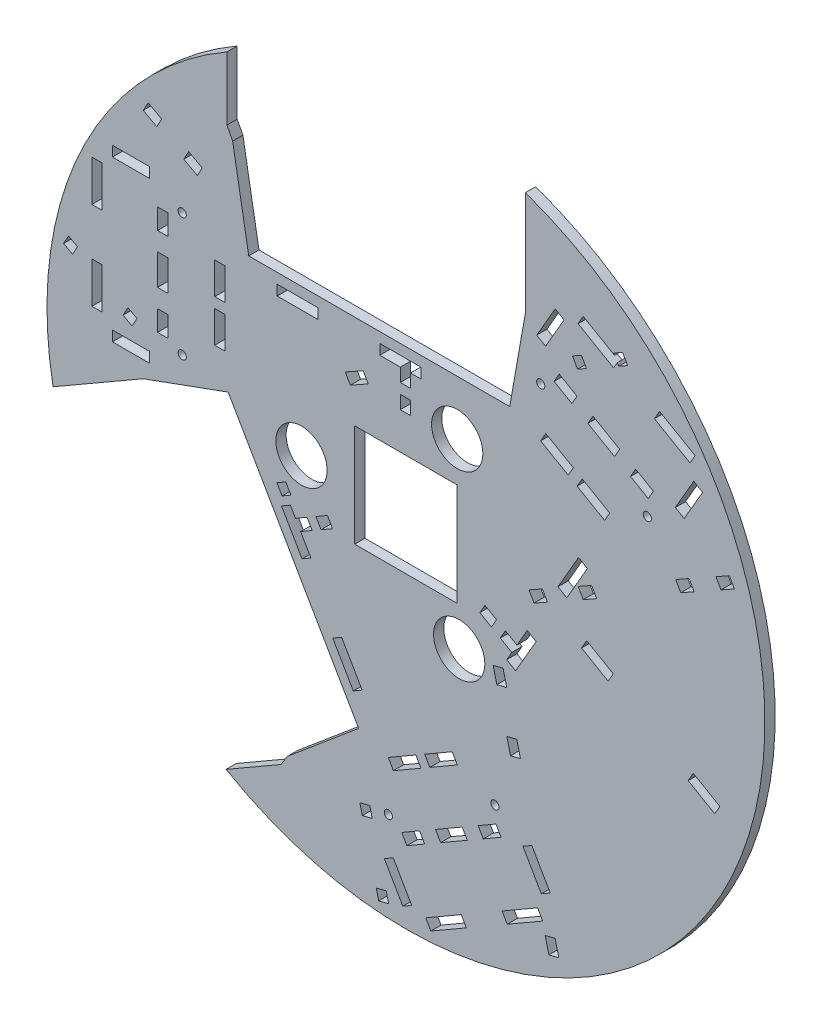
SolidWorks part; units mm, degrees
material "Balsa"
ref_plane "Plan de face" through (0, 0, 0) normal (0, 0, 1) x (1, 0, 0)
ref_plane "Plan de dessus" through (0, 0, 0) normal (0, 1, 0) x (1, 0, 0)
ref_plane "Plan de droite" through (0, 0, 0) normal (1, 0, 0) x (0, 0, -1)
sketch "Esquisse1" plane through (0, 0, 0) normal (0, 0, 1) x (1, 0, 0)
  circle A0 centre (148.0804, -12.1102) radius 175
  dimension "D1" = 350
extrude "Boss.-Extru.1" add sketch "Esquisse1" along normal blind 5
sketch "Esquisse2" plane through (0, 0, 5) normal (0, 0, 1) x (1, 0, 0)
  line L0 (135.3118, 53.7774) -> (135.3118, 48.7774)
  line L1 (5, 72.2774) -> (23, 72.2774)
  line L2 (5, 72.2774) -> (5, 67.2774)
  line L3 (5, 67.2774) -> (23, 67.2774)
  line L4 (23, 72.2774) -> (23, 67.2774)
  line L5 (-5, 62.2774) -> (0, 62.2774)
  line L6 (-5, 62.2774) -> (-5, 42.2774)
  line L7 (-5, 42.2774) -> (0, 42.2774)
  line L8 (0, 62.2774) -> (0, 42.2774)
  line L9 (-5, 19.2774) -> (0, 19.2774)
  line L10 (-5, 19.2774) -> (-5, -0.7226)
  line L11 (-5, -0.7226) -> (0, -0.7226)
  line L12 (0, 19.2774) -> (0, -0.7226)
  line L13 (5, -5.7226) -> (23, -5.7226)
  line L14 (5, -5.7226) -> (5, -10.7226)
  line L15 (5, -10.7226) -> (23, -10.7226)
  line L16 (23, -5.7226) -> (23, -10.7226)
  line L17 (27, 14.2774) -> (32, 14.2774)
  line L18 (27, 14.2774) -> (27, 4.2774)
  line L19 (27, 4.2774) -> (32, 4.2774)
  line L20 (32, 14.2774) -> (32, 4.2774)
  line L21 (27, 38.2774) -> (32, 38.2774)
  line L22 (27, 38.2774) -> (27, 23.2774)
  line L23 (27, 23.2774) -> (32, 23.2774)
  line L24 (32, 38.2774) -> (32, 23.2774)
  line L25 (27, 57.2774) -> (32, 57.2774)
  line L26 (27, 57.2774) -> (27, 47.2774)
  line L27 (27, 47.2774) -> (32, 47.2774)
  line L28 (32, 57.2774) -> (32, 47.2774)
  line L29 (54.86, 48.7774) -> (59.86, 48.7774)
  line L30 (54.86, 48.7774) -> (54.86, 33.2774)
  line L31 (54.86, 33.2774) -> (59.86, 33.2774)
  line L32 (59.86, 48.7774) -> (59.86, 33.2774)
  line L33 (54.86, 28.2774) -> (59.86, 28.2774)
  line L34 (54.86, 28.2774) -> (54.86, 12.7774)
  line L35 (54.86, 12.7774) -> (59.86, 12.7774)
  line L36 (59.86, 28.2774) -> (59.86, 12.7774)
  line L37 (85.3118, 53.7774) -> (105.3118, 53.7774)
  line L38 (85.3118, 53.7774) -> (85.3118, 48.7774)
  line L39 (85.3118, 48.7774) -> (105.3118, 48.7774)
  line L40 (105.3118, 53.7774) -> (105.3118, 48.7774)
  line L41 (145.3118, 37.2774) -> (150.3118, 37.2774)
  line L42 (145.3118, 37.2774) -> (145.3118, 30.7774)
  line L43 (145.3118, 30.7774) -> (150.3118, 30.7774)
  line L44 (150.3118, 37.2774) -> (150.3118, 30.7774)
  line L45 (135.3118, 48.7774) -> (145.3118, 48.7774)
  line L46 (155.3118, 48.7774) -> (135.3118, 48.7774) construction
  line L47 (145.3118, 48.7774) -> (145.3118, 42.2774)
  line L48 (145.3118, 42.2774) -> (150.3118, 42.2774)
  line L49 (150.3118, 42.2774) -> (150.3118, 48.7774)
  line L50 (150.3118, 48.7774) -> (155.3118, 48.7774)
  line L51 (155.3118, 48.7774) -> (155.3118, 53.7774)
  line L52 (155.3118, 53.7774) -> (135.3118, 53.7774)
  line L53 (292.7025, 69.6073) -> (283.7025, 54.0188)
  line L54 (292.7025, 69.6073) -> (288.3723, 72.1073)
  line L55 (288.3723, 72.1073) -> (279.3723, 56.5188)
  line L56 (283.7025, 54.0188) -> (279.3723, 56.5188)
  line L57 (289.0422, 83.2676) -> (286.5422, 78.9374)
  line L58 (289.0422, 83.2676) -> (271.7217, 93.2676)
  line L59 (271.7217, 93.2676) -> (269.2217, 88.9374)
  line L60 (286.5422, 78.9374) -> (269.2217, 88.9374)
  line L61 (251.8031, 104.7676) -> (249.3031, 100.4374)
  line L62 (251.8031, 104.7676) -> (234.4826, 114.7676)
  line L63 (234.4826, 114.7676) -> (231.9826, 110.4374)
  line L64 (249.3031, 100.4374) -> (231.9826, 110.4374)
  line L65 (225.1525, 108.6073) -> (216.1525, 93.0188)
  line L66 (225.1525, 108.6073) -> (220.8223, 111.1073)
  line L67 (220.8223, 111.1073) -> (211.8223, 95.5188)
  line L68 (216.1525, 93.0188) -> (211.8223, 95.5188)
  line L69 (231.473, 79.5547) -> (228.973, 75.2246)
  line L70 (231.473, 79.5547) -> (222.8127, 84.5547)
  line L71 (222.8127, 84.5547) -> (220.3127, 80.2246)
  line L72 (228.973, 75.2246) -> (220.3127, 80.2246)
  line L73 (252.2576, 67.5547) -> (249.7576, 63.2246)
  line L74 (252.2576, 67.5547) -> (239.2672, 75.0547)
  line L75 (239.2672, 75.0547) -> (236.7672, 70.7246)
  line L76 (249.7576, 63.2246) -> (236.7672, 70.7246)
  line L77 (268.7121, 58.0547) -> (266.2121, 53.7246)
  line L78 (268.7121, 58.0547) -> (260.0518, 63.0547)
  line L79 (260.0518, 63.0547) -> (257.5518, 58.7246)
  line L80 (266.2121, 53.7246) -> (257.5518, 58.7246)
  line L81 (247.4209, 38.1773) -> (244.9209, 33.8472)
  line L82 (247.4209, 38.1773) -> (233.9975, 45.9273)
  line L83 (233.9975, 45.9273) -> (231.4975, 41.5972)
  line L84 (244.9209, 33.8472) -> (231.4975, 41.5972)
  line L85 (229.6673, 48.4273) -> (227.1673, 44.0972)
  line L86 (229.6673, 48.4273) -> (216.2439, 56.1773)
  line L87 (216.2439, 56.1773) -> (213.7439, 51.8472)
  line L88 (227.1673, 44.0972) -> (213.7439, 51.8472)
  line L89 (211.5251, -33.996) -> (207.195, -31.496)
  line L90 (236.5251, 9.3053) -> (226.5251, -8.0153)
  line L91 (236.5251, 9.3053) -> (232.195, 11.8053)
  line L92 (232.195, 11.8053) -> (222.195, -5.5153)
  line L93 (226.5251, -8.0153) -> (222.195, -5.5153)
  line L94 (192.2357, -34.4063) -> (189.7357, -38.7364)
  line L95 (192.2357, -34.4063) -> (186.6065, -31.1563)
  line L96 (186.6065, -31.1563) -> (184.1065, -35.4864)
  line L97 (189.7357, -38.7364) -> (184.1065, -35.4864)
  line L98 (207.195, -31.496) -> (202.195, -40.1563)
  line L99 (202.195, -40.1563) -> (196.5658, -36.9063)
  line L100 (196.5658, -36.9063) -> (194.0658, -41.2364)
  line L101 (194.0658, -41.2364) -> (199.695, -44.4864)
  line L102 (199.695, -44.4864) -> (197.195, -48.8165)
  line L103 (197.195, -48.8165) -> (201.5251, -51.3165)
  line L104 (201.5251, -51.3165) -> (211.5251, -33.996)
  line L105 (146.5388, -178.2153) -> (137.5388, -162.6268)
  line L106 (146.5388, -178.2153) -> (150.869, -175.7153)
  line L107 (150.869, -175.7153) -> (141.869, -160.1268)
  line L108 (137.5388, -162.6268) -> (141.869, -160.1268)
  line L109 (160.1991, -181.8755) -> (157.6991, -177.5454)
  line L110 (160.1991, -181.8755) -> (177.5196, -171.8755)
  line L111 (177.5196, -171.8755) -> (175.0196, -167.5454)
  line L112 (157.6991, -177.5454) -> (175.0196, -167.5454)
  line L113 (197.4382, -160.3755) -> (194.9382, -156.0454)
  line L114 (197.4382, -160.3755) -> (214.7587, -150.3755)
  line L115 (214.7587, -150.3755) -> (212.2587, -146.0454)
  line L116 (194.9382, -156.0454) -> (212.2587, -146.0454)
  line L117 (214.0888, -139.2153) -> (205.0888, -123.6268)
  line L118 (214.0888, -139.2153) -> (218.4189, -136.7153)
  line L119 (218.4189, -136.7153) -> (209.4189, -121.1268)
  line L120 (205.0888, -123.6268) -> (209.4189, -121.1268)
  line L121 (185.7683, -130.1627) -> (183.2683, -125.8326)
  line L122 (185.7683, -130.1627) -> (194.4286, -125.1627)
  line L123 (194.4286, -125.1627) -> (191.9286, -120.8326)
  line L124 (183.2683, -125.8326) -> (191.9286, -120.8326)
  line L125 (164.9837, -142.1627) -> (162.4837, -137.8326)
  line L126 (164.9837, -142.1627) -> (177.9741, -134.6627)
  line L127 (177.9741, -134.6627) -> (175.4741, -130.3326)
  line L128 (162.4837, -137.8326) -> (175.4741, -130.3326)
  line L129 (148.5292, -151.6627) -> (146.0292, -147.3326)
  line L130 (148.5292, -151.6627) -> (157.1895, -146.6627)
  line L131 (157.1895, -146.6627) -> (154.6895, -142.3326)
  line L132 (146.0292, -147.3326) -> (154.6895, -142.3326)
  line L133 (141.9604, -123.2852) -> (139.4604, -118.9551)
  line L134 (141.9604, -123.2852) -> (155.3838, -115.5352)
  line L135 (155.3838, -115.5352) -> (152.8838, -111.2051)
  line L136 (139.4604, -118.9551) -> (152.8838, -111.2051)
  line L137 (159.7139, -113.0352) -> (157.2139, -108.7051)
  line L138 (159.7139, -113.0352) -> (173.1373, -105.2852)
  line L139 (173.1373, -105.2852) -> (170.6373, -100.9551)
  line L140 (157.2139, -108.7051) -> (170.6373, -100.9551)
  line L141 (97.4044, -56.1119) -> (101.7345, -53.6119)
  line L142 (122.4044, -99.4132) -> (112.4044, -82.0927)
  line L143 (122.4044, -99.4132) -> (126.7345, -96.9132)
  line L144 (126.7345, -96.9132) -> (116.7345, -79.5927)
  line L145 (112.4044, -82.0927) -> (116.7345, -79.5927)
  line L146 (106.6938, -39.2017) -> (104.1938, -34.8716)
  line L147 (106.6938, -39.2017) -> (112.323, -35.9517)
  line L148 (112.323, -35.9517) -> (109.823, -31.6216)
  line L149 (104.1938, -34.8716) -> (109.823, -31.6216)
  line L150 (101.7345, -53.6119) -> (96.7345, -44.9517)
  line L151 (96.7345, -44.9517) -> (102.3637, -41.7017)
  line L152 (102.3637, -41.7017) -> (99.8637, -37.3716)
  line L153 (99.8637, -37.3716) -> (94.2345, -40.6216)
  line L154 (94.2345, -40.6216) -> (91.7345, -36.2914)
  line L155 (91.7345, -36.2914) -> (87.4044, -38.7914)
  line L156 (87.4044, -38.7914) -> (97.4044, -56.1119)
  line L157 (135.3118, 53.7774) -> (135.3118, 48.7774) construction
  line L158 (105.3118, 53.7774) -> (135.3118, 53.7774) construction
  point P83 (148.0804, -12.1102)
  point P192 (148.0804, -12.1102)
  point P193 (148.0804, -12.1102)
  dimension "D1" = 3
extrude "Enlèv. mat.-Extru.1" cut sketch "Esquisse2" against normal blind 5
sketch "Esquisse6" plane through (0, 0, 5) normal (0, 0, 1) x (1, 0, 0)
  line L0 (93.9998, -7.2151) -> (100.2998, -18.127) construction
  line L1 (206.3213, 102.2219) -> (206.3213, 185.5637)
  line L2 (123.0804, -37.1102) -> (173.0804, -37.1102)
  line L3 (123.0804, -37.1102) -> (123.0804, 12.8898)
  line L4 (123.0804, 12.8898) -> (173.0804, 12.8898)
  line L5 (173.0804, -37.1102) -> (173.0804, 12.8898)
  line L6 (123.0804, -37.1102) -> (173.0804, 12.8898) construction
  line L7 (123.0804, 12.8898) -> (173.0804, -37.1102) construction
  line L8 (206.3213, 185.5637) -> (60.7972, 185.5637)
  line L9 (71.4438, 58.7774) -> (63.5848, 103.3483)
  line L10 (71.4438, 58.7774) -> (198.6608, 58.7774)
  line L11 (198.6608, 58.7774) -> (206.3213, 102.2219)
  line L12 (60.7972, 185.5637) -> (60.7972, 108.6824)
  line L13 (19.9456, -18.8381) -> (-52.2306, -60.5091)
  line L14 (-52.2306, -60.5091) -> (20.5314, -186.5366)
  line L15 (63.5848, 103.3483) -> (60.7972, 108.6824)
  line L16 (125.0083, -113.9232) -> (90.3383, -143.0148)
  line L17 (125.0083, -113.9232) -> (61.3998, -3.7501)
  line L18 (61.3998, -3.7501) -> (19.9456, -18.8381)
  line L20 (236.1714, -21.3074) -> (249.1617, -28.8074)
  line L21 (236.1714, -21.3074) -> (233.6714, -25.6375)
  line L22 (249.1617, -28.8074) -> (246.6617, -33.1375)
  line L23 (233.6714, -25.6375) -> (246.6617, -33.1375)
  line L24 (288.1329, -51.3074) -> (301.1233, -58.8074)
  line L25 (288.1329, -51.3074) -> (285.6329, -55.6375)
  line L26 (301.1233, -58.8074) -> (298.6233, -63.1375)
  line L27 (285.6329, -55.6375) -> (298.6233, -63.1375)
  line L28 (226.5251, -8.0153) -> (236.5251, 9.3053) construction
  line L29 (279.3723, 56.5188) -> (283.7025, 54.0188) construction
  line L31 (64.5427, 103.6743) -> (63.0102, 106.6067) construction
  line L32 (20.5314, -186.5366) -> (87.1126, -148.0959)
  line L33 (90.3383, -143.0148) -> (87.1126, -148.0959)
  circle A0 centre (173.06, 32.2774) radius 12.5
  circle A1 centre (174.0314, -55.9369) radius 12.5
  circle A2 centre (97.1498, -12.671) radius 12.5
  point P2 (148.0804, -12.1102)
  point P8 (148.0804, -12.1102)
  point P10 (148.0804, -12.1102)
  point P35 (148.0804, -12.1102)
  point P48 (148.0804, -12.1102)
  dimension "D12" = 25
  dimension "D3" = 50
  dimension "D4" = 50
  dimension "D5" = 70.8876
  dimension "D6" = 50.5804
  dimension "D7" = 127.217
  dimension "D8" = 100
  dimension "D9" = 100
  dimension "D10" = 145.5241
  dimension "D11" = 43.4444
  dimension "D13" = 5
  dimension "D14" = 15
  dimension "D15" = 15
  dimension "D16" = 45
  dimension "D17" = 15
  dimension "D18" = 89
  dimension "D19" = 2
  dimension "D20" = 1
  dimension "D1" = 3
extrude "Enlèv. mat.-Extru.6" cut sketch "Esquisse6" against normal blind 5
hole_wizard "Trous de centrage Ø4.0mm1" positions "Esquisse7" profile "Esquisse8" hole size "Ø4.0" standard "Ansi Metric" end condition through all
sketch "Esquisse7" plane through (148.0804, -12.1102, -78) normal (0, 0, -1) x (1, 0, 0)
  point P0 (65.7012, -88.0226)
  point P3 (117.6627, -58.0226)
  point P6 (-109.0804, -72.8876)
  point P9 (-109.0804, -12.8876)
  point P12 (-8.5823, 130.9102)
  point P15 (43.3792, 100.9102)
sketch "Esquisse8" plane through (213.7816, 75.9124, -78) normal (1, 0, 0) x (0, 1, 0)
  line L0 (0, 0) -> (0, 83)
  line L1 (0, 83) -> (2, 83)
  line L2 (2, 83) -> (2, 0)
  line L3 (2, 0) -> (0, 0)
  line L4 (0, -6.35) -> (0, 107.95) construction
  dimension "Diamètre du perçage jusqu'au prochain" = 4
  dimension "Profondeur du perçage jusqu'au prochain" = 83
sketch "Esquisse9" plane through (0, 0, 5) normal (0, 0, 1) x (1, 0, 0)
  line L0 (301.6473, 32.8747) -> (299.2005, 37.2351)
  line L1 (301.6473, 32.8747) -> (308.1879, 36.5449)
  line L2 (299.2005, 37.2351) -> (305.7411, 40.9053)
  line L3 (308.1879, 36.5449) -> (305.7411, 40.9053)
  line L4 (282.0254, 21.8642) -> (279.5786, 26.2246)
  line L5 (282.0254, 21.8642) -> (288.566, 25.5344)
  line L6 (279.5786, 26.2246) -> (286.1192, 29.8948)
  line L7 (288.566, 25.5344) -> (286.1192, 29.8948)
  line L8 (241.0375, -1.1356) -> (238.5907, 3.2248)
  line L9 (241.0375, -1.1356) -> (234.4969, -4.8058)
  line L10 (238.5907, 3.2248) -> (232.0501, -0.4454)
  line L11 (234.4969, -4.8058) -> (232.0501, -0.4454)
  line L12 (214.6084, -10.2326) -> (217.0552, -14.593)
  line L13 (214.6084, -10.2326) -> (208.0678, -13.9027)
  line L14 (217.0552, -14.593) -> (210.5146, -18.2632)
  line L15 (208.0678, -13.9027) -> (210.5146, -18.2632)
  line L16 (217.0552, -14.593) -> (234.4969, -4.8058) construction
  line L17 (214.6084, -10.2326) -> (217.0552, -14.593) construction
  line L18 (256.1275, 104.7997) -> (251.7671, 102.3529)
  line L19 (256.1275, 104.7997) -> (253.6807, 109.1601)
  line L20 (251.7671, 102.3529) -> (249.3203, 106.7133)
  line L21 (253.6807, 109.1601) -> (249.3203, 106.7133)
  line L22 (236.0696, 93.5445) -> (231.7091, 91.0977)
  line L23 (236.0696, 93.5445) -> (233.6228, 97.9049)
  line L24 (231.7091, 91.0977) -> (229.2624, 95.4581)
  line L25 (233.6228, 97.9049) -> (229.2624, 95.4581)
  line L26 (129.6754, 33.8428) -> (120.9546, 28.9492)
  line L27 (129.6754, 33.8428) -> (127.2286, 38.2032)
  line L28 (120.9546, 28.9492) -> (118.5078, 33.3096)
  line L29 (127.2286, 38.2032) -> (118.5078, 33.3096)
  line L30 (256.1275, 104.7997) -> (120.9546, 28.9492) construction
  line L31 (301.6473, 32.8747) -> (217.0552, -14.593) construction
  line L32 (-16.4384, 23.2791) -> (-12.0459, 20.8904)
  line L33 (-16.4384, 23.2791) -> (-18.8272, 18.8866)
  line L34 (-12.0459, 20.8904) -> (-14.4347, 16.4979)
  line L35 (-18.8272, 18.8866) -> (-14.4347, 16.4979)
  line L36 (12.552, 7.5136) -> (16.9445, 5.1249)
  line L37 (12.552, 7.5136) -> (10.1633, 3.1211)
  line L38 (16.9445, 5.1249) -> (14.5558, 0.7324)
  line L39 (10.1633, 3.1211) -> (14.5558, 0.7324)
  line L42 (-26.9196, -12.1102) -> (148.0804, -12.1102) construction
  line L44 (22.4127, 98.9071) -> (29.0015, 95.324)
  line L45 (22.4127, 98.9071) -> (20.024, 94.5146)
  line L46 (29.0015, 95.324) -> (26.6128, 90.9315)
  line L47 (20.024, 94.5146) -> (26.6128, 90.9315)
  line L48 (42.179, 88.1579) -> (48.7677, 84.5748)
  line L49 (42.179, 88.1579) -> (39.7903, 83.7654)
  line L50 (48.7677, 84.5748) -> (46.379, 80.1823)
  line L51 (39.7903, 83.7654) -> (46.379, 80.1823)
  line L53 (148.0804, -12.1102) -> (9.6568, -109.2191) construction
  line L55 (129.7636, 187.6323) -> (148.0804, -12.1102) construction
  arc A0 (60.3638, -163.5394) -> (206.3213, 152.9141) centre (148.0804, -12.1102) ccw construction
  line B0 (154.106, -73.5915) -> (185.6214, -199.5155) construction
  line B1 (126.7996, -149.8343) -> (125.5857, -144.9839)
  line B2 (130.4361, -143.77) -> (125.5857, -144.9839)
  line B3 (131.65, -148.6204) -> (126.7996, -149.8343)
  line B4 (131.65, -148.6204) -> (130.4361, -143.77)
  line B5 (134.8115, -181.8469) -> (133.5976, -176.9965)
  line B6 (138.448, -175.7826) -> (133.5976, -176.9965)
  line B7 (139.6619, -180.633) -> (134.8115, -181.8469)
  line B8 (139.6619, -180.633) -> (138.448, -175.7826)
  line B9 (190.562, -54.5014) -> (195.4124, -53.2875)
  line B10 (197.2333, -60.5631) -> (195.4124, -53.2875)
  line B11 (192.3829, -61.777) -> (190.562, -54.5014)
  line B12 (192.3829, -61.777) -> (197.2333, -60.5631)
  line B13 (202.089, -79.9647) -> (197.2386, -81.1786)
  line B14 (199.0595, -88.4542) -> (197.2386, -81.1786)
  line B15 (203.9099, -87.2403) -> (202.089, -79.9647)
  line B16 (203.9099, -87.2403) -> (199.0595, -88.4542)
  line B17 (222.6043, -161.9364) -> (217.7539, -163.1503)
  line B18 (215.933, -155.8747) -> (217.7539, -163.1503)
  line B19 (220.7834, -154.6608) -> (222.6043, -161.9364)
  line B20 (220.7834, -154.6608) -> (215.933, -155.8747)
  dimension "D9" = 170.2546
  dimension "D1" = 10
  dimension "D2" = 5
  dimension "D3" = 7.5
  dimension "D4" = 7.5
  dimension "D5" = 7.5
  dimension "D6" = 7.5
  dimension "D7" = 5
  dimension "D8" = 117
  dimension "D10" = 167.3371
  dimension "D11" = 69
  dimension "D12" = 35.051
sketch_block_instance "Bloc1-1"
sketch_block "Bloc1"
extrude "Holes catchers of glass" cut sketch "Esquisse9" against normal blind 10
sketch "Esquisse10" plane through (0, 0, 5) normal (0, 0, 1) x (1, 0, 0)
  line L0 (89.4961, -27.6144) -> (91.9961, -31.9445)
  line L1 (89.4961, -27.6144) -> (85.1672, -30.1137)
  line L2 (91.9961, -31.9445) -> (87.6672, -34.4438)
  line L3 (85.1672, -30.1137) -> (87.6672, -34.4438)
  dimension "D1" = 4.9986
extrude "Holes boards servo" cut sketch "Esquisse10" against normal blind 10
